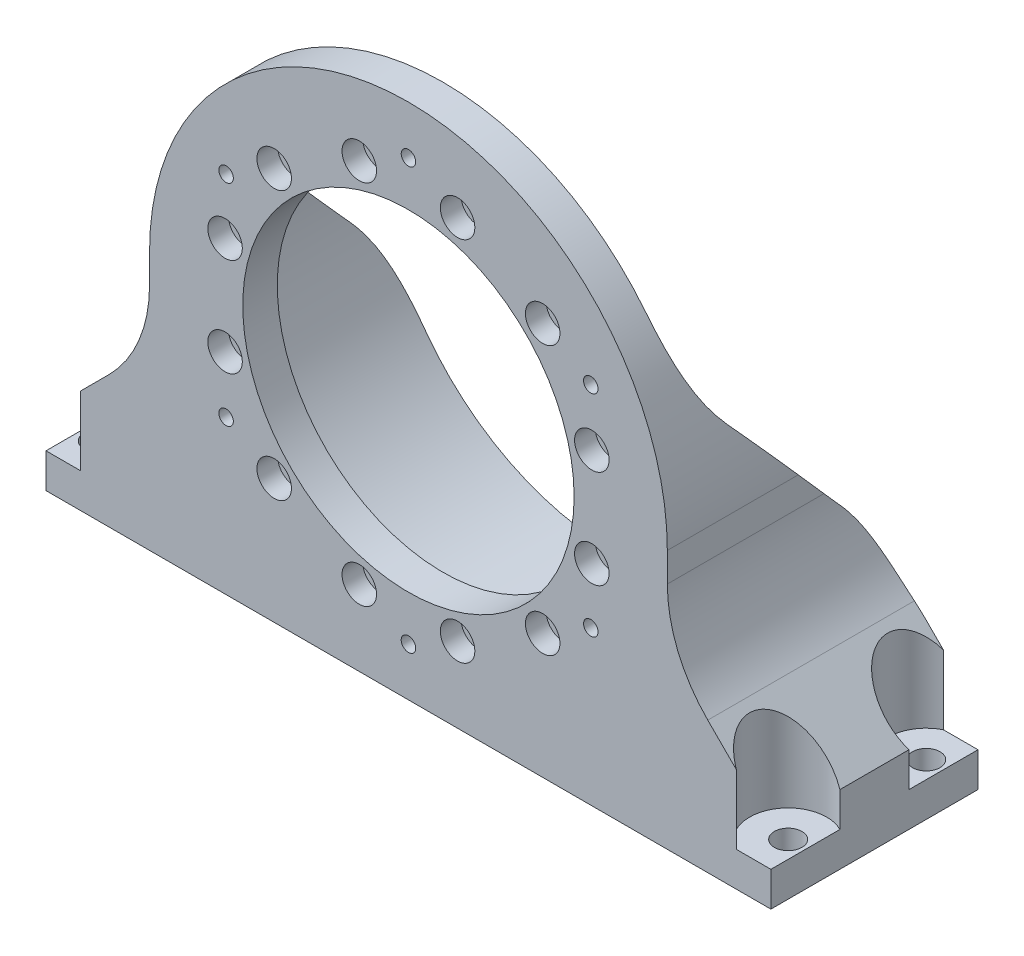
SolidWorks part; units mm, degrees
ref_plane "Front Plane" through (0, 0, 0) normal (0, 0, 1) x (1, 0, 0)
ref_plane "Top Plane" through (0, 0, 0) normal (0, 1, 0) x (1, 0, 0)
ref_plane "Right Plane" through (0, 0, 0) normal (1, 0, 0) x (0, 0, -1)
sketch "Sketch1" plane through (0, 0, 0) normal (0, 0, 1) x (1, 0, 0)
  line L0 (-75, 0) -> (-75, -75)
  line L2 (75, -75) -> (75, 0)
  line L7 (-75, -75) -> (75, -75)
  circle A0 centre (0, 0) radius 48
  arc A1 (75, 0) -> (-75, 0) centre (0, 0) ccw
  arc A2 (-75, 0) -> (0, -75) centre (0, 0) ccw construction
  arc A3 (0, -75) -> (75, 0) centre (0, 0) ccw construction
  dimension "D1" = 150
  dimension "D2" = 96
extrude "Boss-Extrude1" add sketch "Sketch1" along normal blind 10
sketch "Sketch2" plane through (0, 0, 10) normal (0, 0, 1) x (1, 0, 0)
  line L0 (0, 0) -> (0, 61) construction
  circle A0 centre (0, 61) radius 2.1
  circle A1 centre (52.8275, 30.5) radius 2.1
  circle A2 centre (52.8275, -30.5) radius 2.1
  circle A3 centre (0, -61) radius 2.1
  circle A4 centre (-52.8275, -30.5) radius 2.1
  circle A5 centre (-52.8275, 30.5) radius 2.1
  point P16 (0, 0)
  dimension "D1" = 4.2
  dimension "D2" = 61
  dimension "D3" = 6
extrude "Cut-Extrude1" cut sketch "Sketch2" against normal through all
sketch "Sketch3" plane through (0, 0, 10) normal (0, 0, 1) x (1, 0, 0)
  line L0 (0, 0) -> (14.235, 53.1259) construction
  line L1 (0, 0) -> (0, 26.2737) construction
  circle A0 centre (14.235, 53.1259) radius 1.6
  circle A1 centre (38.8909, 38.8909) radius 1.6
  circle A2 centre (53.1259, 14.235) radius 1.6
  circle A3 centre (53.1259, -14.235) radius 1.6
  circle A4 centre (38.8909, -38.8909) radius 1.6
  circle A5 centre (14.235, -53.1259) radius 1.6
  circle A6 centre (-14.235, -53.1259) radius 1.6
  circle A7 centre (-38.8909, -38.8909) radius 1.6
  circle A8 centre (-53.1259, -14.235) radius 1.6
  circle A9 centre (-53.1259, 14.235) radius 1.6
  circle A10 centre (-38.8909, 38.8909) radius 1.6
  circle A11 centre (-14.235, 53.1259) radius 1.6
  point P29 (0, 0)
  dimension "D1" = 3.2
  dimension "D2" = 55
  dimension "D3" = 15
  dimension "D4" = 12
extrude "Cut-Extrude2" cut sketch "Sketch3" against normal through all
sketch "Sketch4" plane through (0, 0, 0) normal (0, 0, -1) x (-1, 0, 0)
  circle A0 centre (-52.8275, 30.5) radius 2.75
  circle A1 centre (0, 61) radius 2.75
  circle A2 centre (52.8275, 30.5) radius 2.75
  circle A3 centre (52.8275, -30.5) radius 2.75
  circle A4 centre (0, -61) radius 2.75
  circle A5 centre (-52.8275, -30.5) radius 2.75
  dimension "D1" = 5.5
extrude "Cut-Extrude3" cut sketch "Sketch4" against normal blind 6.5
sketch "Sketch5" plane through (0, 0, 10) normal (0, 0, 1) x (1, 0, 0)
  circle A0 centre (14.235, 53.1259) radius 5
  circle A1 centre (-14.235, 53.1259) radius 5
  circle A2 centre (38.8909, 38.8909) radius 5
  circle A3 centre (53.1259, 14.235) radius 5
  circle A4 centre (53.1259, -14.235) radius 5
  circle A5 centre (38.8909, -38.8909) radius 5
  circle A6 centre (14.235, -53.1259) radius 5
  circle A7 centre (-14.235, -53.1259) radius 5
  circle A8 centre (-38.8909, -38.8909) radius 5
  circle A9 centre (-53.1259, -14.235) radius 5
  circle A10 centre (-53.1259, 14.235) radius 5
  circle A11 centre (-38.8909, 38.8909) radius 5
  point P1 (0, 0)
  point P28 (0, 0)
  dimension "D1" = 10
extrude "Cut-Extrude4" cut sketch "Sketch5" against normal offset from surface (6 mm away) 4 up to face at (50.0775, -30.5, 0)
sketch "Sketch6" plane through (0, 0, 0) normal (0, 0, -1) x (-1, 0, 0)
  line L0 (-68, 0) -> (-68, 31.6386) construction
  line L2 (-75, -25) -> (-105, -55)
  line L3 (-105, -55) -> (-105, -75)
  line L4 (-105, -75) -> (-75, -75)
  line L5 (-75, 0) -> (-75, -75)
  line L6 (-75, -75) -> (75, -75)
  line L7 (75, -75) -> (75, 0)
  line L8 (-75, 0) -> (-75, -25)
  line L9 (-75, -75) -> (75, -75)
  line L11 (-68, 31.6386) -> (-60.1914, 31.6386)
  line L12 (0, -65) -> (0, -75) construction
  line L13 (68, 0) -> (68, 31.6386) construction
  line L14 (68, 31.6386) -> (60.1914, 31.6386)
  line L15 (75, 0) -> (75, -25)
  line L16 (105, -75) -> (75, -75)
  line L17 (105, -55) -> (105, -75)
  line L18 (75, -25) -> (105, -55)
  arc A0 (-68, 0) -> (68, 0) centre (0, 0) ccw
  arc A1 (75, 0) -> (-75, 0) centre (0, 0) ccw construction
  arc A2 (60.1914, 31.6386) -> (68, 0) centre (0, 0) cw
  arc A3 (75, 0) -> (-75, 0) centre (0, 0) ccw
  arc A5 (-68, 31.6386) -> (-75, 0) centre (0, 0) ccw
  arc A6 (-60.1914, 31.6386) -> (-68, 0) centre (0, 0) ccw
  arc A7 (68, 31.6386) -> (75, 0) centre (0, 0) cw
  point P8 (-59.3491, 26.2458)
  dimension "D5" = 68
  dimension "D2" = 30
  dimension "D3" = 20
  dimension "D4" = 135
  dimension "D1" = 0
extrude "Boss-Extrude2" add sketch "Sketch6" along normal blind 50 and the other way up to surface (10 mm away) other way up to face at (19.235, 53.1259, 10)
sketch "Sketch7" plane through (0, 0, 0) normal (1, 0, 0) x (0, 0, -1)
  line L0 (0, 31.6386) -> (50, -25)
  line L1 (50, -25) -> (50, 31.6386)
  line L2 (50, 31.6386) -> (0, 31.6386)
  line L3 (50, 0) -> (50, 31.6386) construction
  line L4 (-10, -25) -> (50, -25) construction
  point P6 (15, 25.0865)
  point P9 (0, 25.9808)
  point P11 (40, -31.906)
extrude "Cut-Extrude5" cut sketch "Sketch7" against normal through all both and the other way through all
sketch "Sketch8" plane through (0, -75, 0) normal (0, -1, 0) x (1, 0, 0)
  line L0 (-100, 0) -> (-100, -40) construction
  line L1 (-105, 10) -> (-105, -50) construction
  line L2 (0, 0) -> (0, -26.9381) construction
  circle A0 centre (-100, 0) radius 4
  circle A1 centre (-100, -40) radius 4
  circle A2 centre (100, -40) radius 4
  circle A3 centre (100, 0) radius 4
  point P6 (-105, -20)
  point P7 (-100, -20)
  dimension "D1" = 8
  dimension "D2" = 40
  dimension "D3" = 200
extrude "Cut-Extrude6" cut sketch "Sketch8" against normal through all both
sketch "Sketch9" plane through (0, -75, 0) normal (0, -1, 0) x (1, 0, 0)
  circle A0 centre (-100, 0) radius 11.1803
  circle A1 centre (-100, -40) radius 11.1803
  circle A2 centre (100, -40) radius 11.1803
  circle A3 centre (100, 0) radius 11.1803
extrude "Cut-Extrude7" cut sketch "Sketch9" against normal through all from offset 10 offset against normal yes
fillet "Fillet1" radius 40 6 edges at (-75, -25, -20) (75, -25, -20) (-64.0957, 31.6386, 0) (64.0957, 31.6386, 0) (-69.1188, -25, -50) (69.1188, -25, -50)
sketch "Sketch10" plane through (0, 0, 4) normal (0, 0, 1) x (1, 0, 0)
  circle A0 centre (14.235, 53.1259) radius 5
  circle A1 centre (-14.235, 53.1259) radius 5
  circle A2 centre (-14.235, 53.1259) radius 5
  circle A3 centre (38.8909, 38.8909) radius 5
  circle A4 centre (53.1259, 14.235) radius 5
  circle A5 centre (53.1259, -14.235) radius 5
  circle A6 centre (38.8909, -38.8909) radius 5
  circle A7 centre (14.235, -53.1259) radius 5
  circle A8 centre (-14.235, -53.1259) radius 5
  circle A9 centre (-38.8909, -38.8909) radius 5
  circle A10 centre (-53.1259, -14.235) radius 5
  circle A11 centre (-53.1259, 14.235) radius 5
  circle A12 centre (-38.8909, 38.8909) radius 5
  point P0 (0, 0)
  point P27 (0, 0)
  dimension "D1" = 0
  dimension "D2" = 12
extrude "Boss-Extrude3" add sketch "Sketch10" against normal blind 0.2
